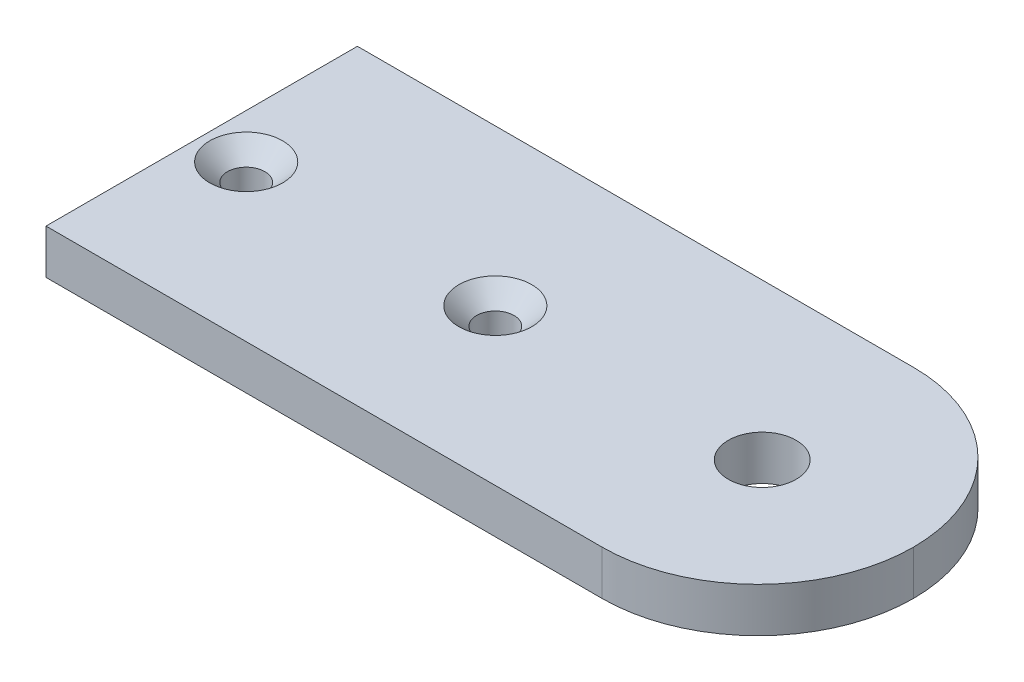
SolidWorks part; units mm, degrees
ref_plane "Front Plane" through (0, 0, 0) normal (0, 0, 1) x (1, 0, 0)
ref_plane "Top Plane" through (0, 0, 0) normal (0, 1, 0) x (1, 0, 0)
ref_plane "Right Plane" through (0, 0, 0) normal (1, 0, 0) x (0, 0, -1)
sketch "Sketch1" plane through (0, 0, 0) normal (0, 1, 0) x (1, 0, 0)
  line L1 (0, 0) -> (80, 0)
  line L2 (0, 0) -> (0, -35)
  line L3 (0, -35) -> (80, -35)
  line L4 (80, 0) -> (80, -35)
  dimension "D1" = 35
  dimension "D2" = 80
extrude "Boss-Extrude1" add sketch "Sketch1" along normal blind 5
hole_wizard "CSK for M3.5 Flat Head Machine Screw1" positions "Sketch2" profile "Sketch4" countersink size "M3.5" standard "ANSI Metric" end condition through all
sketch "Sketch2" plane through (0, 5, 0) normal (0, 1, 0) x (1, 0, 0)
  line L0 (0, -17.5) -> (56.1989, -17.5) construction
  line L1 (0, 0) -> (0, -35) construction
  point P6 (5, -17.5)
  point P8 (33, -17.5)
  point P17 (77.6329, 6.3497)
  point P18 (0, 0)
  dimension "D1" = 28
  dimension "D2" = 5
sketch "Sketch4" plane through (33, 5, 17.5) normal (1, 0, 0) x (0, 0, 1)
  line L0 (0, 0) -> (0, 5)
  line L1 (0, 5) -> (2.1, 5)
  line L2 (2.1, 5) -> (2.1, 2)
  line L3 (2.1, 2) -> (4.1, 0)
  line L5 (4.1, 0) -> (0, 0)
  line L6 (-2.1, 2) -> (-4.1, 0) construction
  line L11 (0, -6.35) -> (0, 107.95) construction
  dimension "Thru Hole Dia." = 4.2
  dimension "Thru Hole Depth" = 5
  dimension "Near C'Sink Dia." = 8.2
  dimension "Near C'Sink Angle" = 90
sketch "Sketch5" plane through (0, 0, 0) normal (0, -1, 0) x (1, 0, 0)
  line L0 (63, 17.5) -> (33, 17.5) construction
  circle A0 centre (63, 17.5) radius 3.81
  dimension "D1" = 7.62
  dimension "D2" = 30
extrude "Cut-Extrude1" cut sketch "Sketch5" against normal blind 5
fillet "Fillet1" radius 17.5 2 edges at (80, 2.5, 35) (80, 2.5, 0)
